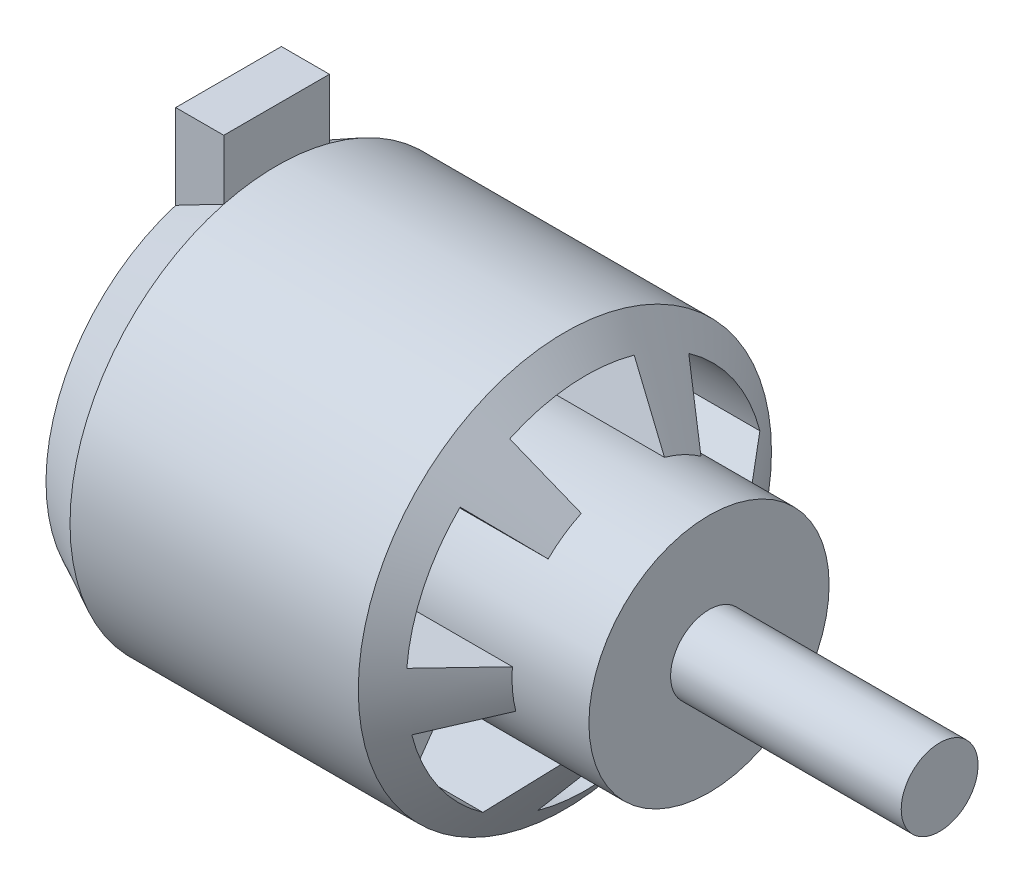
SolidWorks part; units mm, degrees
ref_plane "Front" through (0, 0, 0) normal (0, 0, 1) x (1, 0, 0)
ref_plane "Top" through (0, 0, 0) normal (0, 1, 0) x (1, 0, 0)
ref_plane "Right" through (0, 0, 0) normal (1, 0, 0) x (0, 0, -1)
sketch "Sketch1" plane through (0, 0, 0) normal (0, 0, 1) x (1, 0, 0)
  line L0 (0, 0) -> (0, 19)
  line L1 (0, 19) -> (5, 21.5)
  line L2 (5, 21.5) -> (35, 21.5)
  line L3 (35, 21.5) -> (42, 12.5)
  line L4 (42, 12.5) -> (50, 12.5)
  line L5 (50, 12.5) -> (50, 4)
  line L6 (50, 4) -> (74, 4)
  line L7 (74, 4) -> (74, 0)
  line L8 (0, 0) -> (74, 0) construction
  line L9 (0, 0) -> (74, 0)
  point P2 (54.7853, 1.0586)
  point P11 (0, 0)
  point P12 (0, 0)
  point P13 (49.8529, 9.3658)
  point P14 (0, 0)
  point P15 (50.8856, 12.5)
  point P16 (46.5418, 12.5)
  dimension "D1" = 38
  dimension "D2" = 43
  dimension "D3" = 5
  dimension "D4" = 42
  dimension "D5" = 30
  dimension "D6" = 25
  dimension "D7" = 8
  dimension "D8" = 24
  dimension "D9" = 8
revolve "Revolve1" add sketch "Sketch1" angle 360 about L8
sketch "Sketch2" plane through (50, 0, 0) normal (1, 0, 0) x (0, 0, -1)
  line L0 (18.6304, -1.6116) -> (12.4535, -1.0773)
  line L1 (13.078, -13.3662) -> (8.742, -8.9346)
  line L2 (7.9195, -16.9402) -> (5.2938, -11.3237)
  line L3 (-5.0365, -18.009) -> (-3.3666, -12.0381)
  line L4 (-10.7109, -15.3286) -> (-7.1597, -10.2464)
  line L5 (-18.1145, -4.6428) -> (-12.1086, -3.1035)
  line L6 (-18.6304, 1.6116) -> (-12.4535, 1.0773)
  line L7 (-13.078, 13.3662) -> (-8.742, 8.9346)
  line L8 (-7.9195, 16.9402) -> (-5.2938, 11.3237)
  line L9 (5.0365, 18.009) -> (3.3666, 12.0381)
  line L10 (10.7109, 15.3286) -> (7.1597, 10.2464)
  line L11 (18.1145, 4.6428) -> (12.1086, 3.1035)
  circle A0 centre (0, 0) radius 12.5 construction
  arc A1 (8.742, -8.9346) -> (12.4535, -1.0773) centre (0, 0) ccw
  arc A2 (-5.0365, -18.009) -> (7.9195, -16.9402) centre (0, 0) ccw
  arc A3 (-3.3666, -12.0381) -> (5.2938, -11.3237) centre (0, 0) ccw
  circle A4 centre (0, 0) radius 18.7
  arc A5 (13.078, -13.3662) -> (18.6304, -1.6116) centre (0, 0) ccw
  arc A6 (-18.1145, -4.6428) -> (-10.7109, -15.3286) centre (0, 0) ccw
  arc A7 (-12.1086, -3.1035) -> (-7.1597, -10.2464) centre (0, 0) ccw
  arc A8 (-13.078, 13.3662) -> (-18.6304, 1.6116) centre (0, 0) ccw
  arc A9 (-8.742, 8.9346) -> (-12.4535, 1.0773) centre (0, 0) ccw
  arc A10 (5.0365, 18.009) -> (-7.9195, 16.9402) centre (0, 0) ccw
  arc A11 (3.3666, 12.0381) -> (-5.2938, 11.3237) centre (0, 0) ccw
  arc A12 (18.1145, 4.6428) -> (10.7109, 15.3286) centre (0, 0) ccw
  arc A13 (12.1086, 3.1035) -> (7.1597, 10.2464) centre (0, 0) ccw
  point P31 (0, 0)
  dimension "D2" = 13
  dimension "D1" = 2.8
  dimension "D3" = 6
extrude "Cut-Extrude1" cut sketch "Sketch2" against normal blind 20
sketch "Sketch3" plane through (0, 0, 0) normal (0, 1, 0) x (1, 0, 0)
  line L0 (0, 19) -> (0, -19) construction
  line L1 (0, 5.5) -> (5, 5.5)
  line L2 (0, 5.5) -> (0, -5.5)
  line L3 (0, -5.5) -> (5, -5.5)
  line L4 (5, 5.5) -> (5, -5.5)
  line L5 (5, -21.5) -> (5, 21.5) construction
  line L6 (5, 0) -> (0, 0) construction
  line L7 (5, -21.5) -> (35, -21.5) construction
  line L8 (35, 21.5) -> (5, 21.5) construction
  dimension "D1" = 11
extrude "Boss-Extrude1" add sketch "Sketch3" along normal blind 27
